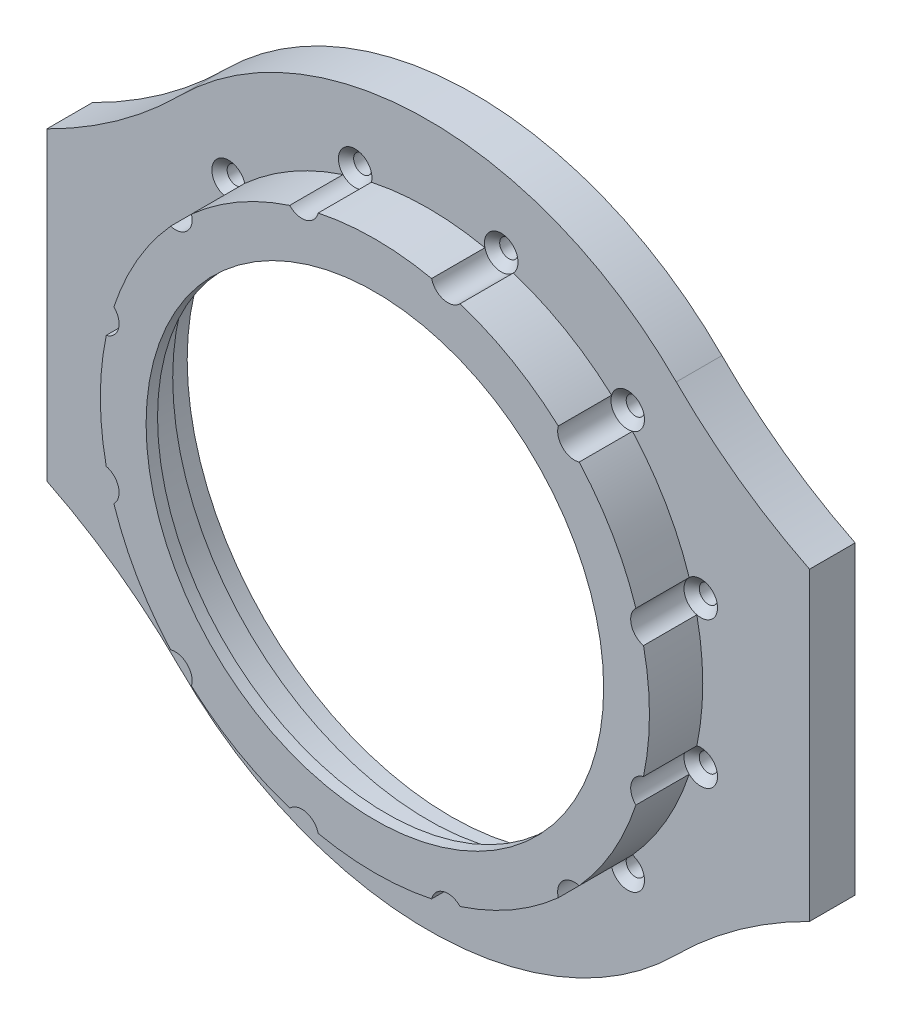
SolidWorks part; units mm, degrees
ref_plane "前视基准面" through (0, 0, 0) normal (0, 0, 1) x (1, 0, 0)
ref_plane "上视基准面" through (0, 0, 0) normal (0, 1, 0) x (1, 0, 0)
ref_plane "右视基准面" through (0, 0, 0) normal (1, 0, 0) x (0, 0, -1)
sketch "草图3" plane through (0, 0, 0) normal (0, 0, 1) x (1, 0, 0)
  circle A0 centre (0, 0) radius 34.6
  circle A1 centre (0, 0) radius 46
extrude "凸台-拉伸2" add sketch "草图3" along normal blind 3
ref_plane "基准面5" through (0, 0, 3) normal (0, 0, 1) x (1, 0, 0)
sketch "草图5" plane through (0, 0, 3) normal (0, 0, 1) x (1, 0, 0)
  circle A0 centre (0, 0) radius 33.5
  circle A1 centre (0, 0) radius 36
extrude "凸台-拉伸3" add sketch "草图5" along normal blind 5.49
sketch "草图2" plane through (0, 0, 0) normal (0, 0, 1) x (1, 0, 0)
  circle A0 centre (0, 0) radius 41.6
  circle A1 centre (0, 0) radius 46
extrude "凸台-拉伸1" add sketch "草图2" against normal blind 2.98
sketch "草图6" plane through (0, 0, 8.49) normal (0, 0, 1) x (1, 0, 0)
  circle A0 centre (0, 0) radius 30
  circle A1 centre (0, 0) radius 36
extrude "凸台-拉伸4" add sketch "草图6" along normal blind 1.5
sketch "草图8" plane through (0, 0, 0) normal (0, 0, 1) x (1, 0, 0)
  line L1 (-50, -20) -> (-50, 20)
  line L3 (50, -20) -> (50, 20)
  circle A0 centre (0, 0) radius 46 construction
  arc A2 (-50, 20) -> (-32.5269, 32.5269) centre (-79.2531, 79.2531) ccw
  arc A3 (-50, -20) -> (-32.5269, -32.5269) centre (-79.2531, -79.2531) cw
  arc A4 (-32.5269, 32.5269) -> (-32.5269, -32.5269) centre (0, 0) ccw
  arc A5 (32.5269, 32.5269) -> (32.5269, -32.5269) centre (0, 0) cw
  arc A6 (50, -20) -> (32.5269, -32.5269) centre (79.2531, -79.2531) ccw
  arc A7 (50, 20) -> (32.5269, 32.5269) centre (79.2531, 79.2531) cw
extrude "凸台-拉伸5" add sketch "草图8" along normal blind 3 and the other way blind 2.98
hole_wizard "M2 锥坑平头的锥孔1" positions "3D草图3" profile "草图12" countersink size "M2" standard "BSI" end condition through all
sketch3d "3D草图3"
  line L2 (0, 0, 0) -> (0, 37, 0)
  line L3 (0, 0, 0) -> (11.5811, 0, 0)
  point P55 (9.5763, 35.7393, 3)
  point P76 (26.163, 26.163, 3)
  point P83 (35.7393, 9.5763, 3)
  point P96 (-35.7393, 9.5763, 3)
  point P97 (-26.163, 26.163, 3)
  point P98 (-9.5763, 35.7393, 3)
  point P99 (35.7393, -9.5763, 3)
  point P100 (26.163, -26.163, 3)
  point P101 (9.5763, -35.7393, 3)
  point P102 (-9.5763, -35.7393, 3)
  point P103 (-26.163, -26.163, 3)
  point P104 (-35.7393, -9.5763, 3)
sketch "草图12" plane through (-35.7393, -9.5763, 3) normal (1, 0, 0) x (0, -1, 0)
  line L0 (0, 0) -> (0, 5.98)
  line L1 (0, 5.98) -> (1.2, 5.98)
  line L2 (1.2, 5.98) -> (1.2, 1)
  line L3 (1.2, 1) -> (2.2, 0)
  line L5 (2.2, 0) -> (0, 0)
  line L6 (-1.2, 1) -> (-2.2, 0) construction
  line L11 (0, -6.35) -> (0, 107.95) construction
  dimension "通孔孔直径" = 2.4
  dimension "通孔孔深度" = 5.98
  dimension "近端锥形沉头孔直径" = 4.4
  dimension "近端锥形沉头孔角度" = 90
sketch "草图13" plane through (0, 0, 3) normal (0, 0, 1) x (1, 0, 0)
  line L0 (0, 0) -> (0, 10.9464)
  line L1 (0, 0) -> (8.3109, 0)
  circle A0 centre (-35.7393, 9.5763) radius 2.2
  circle A1 centre (-26.163, 26.163) radius 2.2
  circle A2 centre (-9.5763, 35.7393) radius 2.2
  circle A3 centre (-9.5763, -35.7393) radius 2.2
  circle A4 centre (-26.163, -26.163) radius 2.2
  circle A5 centre (-35.7393, -9.5763) radius 2.2
  circle A6 centre (9.5763, -35.7393) radius 2.2
  circle A7 centre (26.163, -26.163) radius 2.2
  circle A8 centre (9.5763, 35.7393) radius 2.2
  circle A9 centre (26.163, 26.163) radius 2.2
  circle A10 centre (35.7393, -9.5763) radius 2.2
  circle A11 centre (35.7393, 9.5763) radius 2.2
extrude "切除-拉伸1" cut sketch "草图13" along normal up to next contours A5 | A4 | A0 | A1 | A2 | A9 | A11 | A10 | A6 | A3 | A8 | A7 region at (-35.7393, 9.5763, 3) region at (-26.163, 26.163, 3) region at (-9.5763, 35.7393, 3) region at (-9.5763, -35.7393, 3) region at (-26.163, -26.163, 3) region at (-35.7393, -9.5763, 3) region at (9.5763, -35.7393, 3) region at (26.163, 26.163, 3) region at (35.7393, -9.5763, 3) region at (35.7393, 9.5763, 3)
